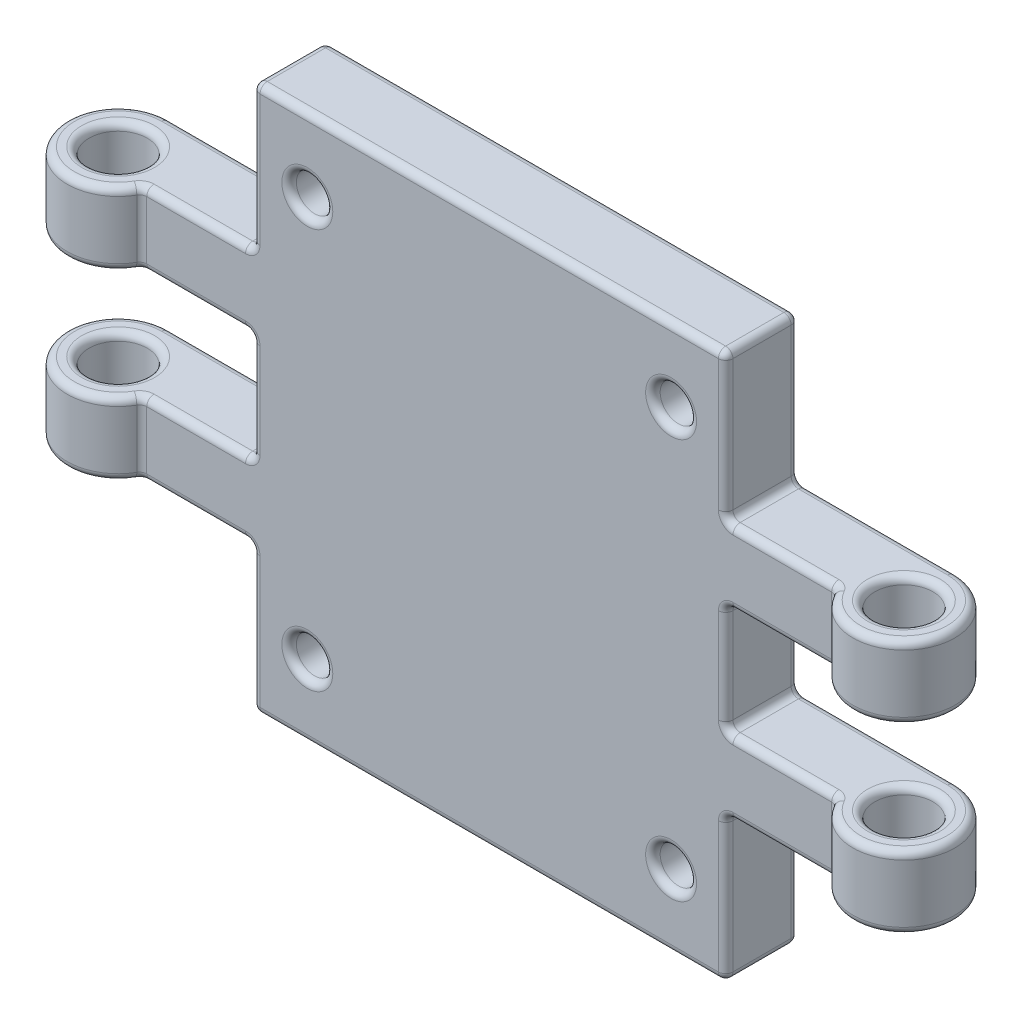
SolidWorks part; units mm, degrees
ref_plane "Front Plane" through (0, 0, 0) normal (0, 0, 1) x (1, 0, 0)
ref_plane "Top Plane" through (0, 0, 0) normal (0, 1, 0) x (1, 0, 0)
ref_plane "Right Plane" through (0, 0, 0) normal (1, 0, 0) x (0, 0, -1)
sketch "Sketch1" plane through (0, 0, 0) normal (0, 0, 1) x (1, 0, 0)
  line L0 (-47.5, 7.5) -> (-47.5, 17.5)
  line L1 (-47.5, -17.5) -> (47.5, -17.5)
  line L2 (-47.5, -17.5) -> (-47.5, 17.5) construction
  line L3 (-47.5, 17.5) -> (47.5, 17.5)
  line L4 (47.5, -17.5) -> (47.5, 17.5) construction
  line L5 (-47.5, -17.5) -> (47.5, 17.5) construction
  line L6 (-47.5, 17.5) -> (47.5, -17.5) construction
  line L7 (60.5, 7.5) -> (47.5, 7.5)
  line L8 (60.5, 7.5) -> (60.5, 17.5)
  line L9 (60.5, 17.5) -> (47.5, 17.5)
  line L10 (47.5, 7.5) -> (47.5, 17.5)
  line L11 (60.5, 7.5) -> (47.5, 17.5) construction
  line L12 (60.5, 17.5) -> (47.5, 7.5) construction
  line L13 (60.5, -7.5) -> (47.5, -7.5)
  line L14 (60.5, -7.5) -> (60.5, -17.5)
  line L15 (60.5, -17.5) -> (47.5, -17.5)
  line L16 (47.5, -7.5) -> (47.5, -17.5)
  line L17 (60.5, -7.5) -> (47.5, -17.5) construction
  line L18 (60.5, -17.5) -> (47.5, -7.5) construction
  line L19 (-60.5, 7.5) -> (-47.5, 7.5)
  line L20 (-60.5, 7.5) -> (-60.5, 17.5)
  line L21 (-60.5, 17.5) -> (-47.5, 17.5)
  line L22 (-47.5, 7.5) -> (-47.5, 17.5)
  line L23 (-60.5, 7.5) -> (-47.5, 17.5) construction
  line L24 (-60.5, 17.5) -> (-47.5, 7.5) construction
  line L25 (-60.5, -7.5) -> (-47.5, -7.5)
  line L26 (-60.5, -7.5) -> (-60.5, -17.5)
  line L27 (-60.5, -17.5) -> (-47.5, -17.5)
  line L28 (-47.5, -7.5) -> (-47.5, -17.5)
  line L29 (-60.5, -7.5) -> (-47.5, -17.5) construction
  line L30 (-60.5, -17.5) -> (-47.5, -7.5) construction
  line L33 (47.5, 17.5) -> (-47.5, 17.5)
  line L35 (-32.5, 37.5) -> (-32.5, 17.5)
  line L36 (-32.5, 37.5) -> (32.5, 37.5)
  line L39 (-47.5, -17.5) -> (47.5, -17.5)
  line L41 (32.5, 37.5) -> (32.5, 17.5)
  line L42 (55, 0) -> (-55, 0) construction
  line L43 (-47.5, -7.5) -> (-47.5, -17.5)
  line L44 (47.5, 17.5) -> (47.5, 7.5)
  line L45 (47.5, -7.5) -> (47.5, -17.5)
  line L46 (47.5, -7.5) -> (32.5, -7.5)
  line L47 (32.5, -7.5) -> (32.5, 7.5)
  line L48 (32.5, 7.5) -> (47.5, 7.5)
  line L49 (-47.5, 7.5) -> (-32.5, 7.5)
  line L50 (-32.5, 7.5) -> (-32.5, -7.5)
  line L51 (-32.5, -7.5) -> (-47.5, -7.5)
  line L52 (-54, -12.5) -> (54, -12.5) construction
  line L53 (-54, 12.5) -> (54, 12.5) construction
  line L54 (-32.5, -37.5) -> (-32.5, -17.5)
  line L55 (32.5, -37.5) -> (32.5, -17.5)
  line L56 (-32.5, -37.5) -> (32.5, -37.5)
  point P0 (0, 0)
  point P6 (54, 12.5)
  point P7 (54, -12.5)
  point P11 (-54, 12.5)
  point P15 (-54, -12.5)
  dimension "D1" = 20
  dimension "D2" = 108
  dimension "D3" = 10
  dimension "D4" = 15
  dimension "D6" = 13
  dimension "D7" = 15
extrude "Boss-Extrude1" add sketch "Sketch1" along normal blind 10 contours L10 L7 L8 L9 | L50 L51 L28 L1 L16 L46 L47 L48 L10 L3 L0 L49 | L13 L16 L15 L14 | L21 L20 L19 L0 | L28 L25 L26 L27 | L41 L36 L35 L33 | L54 L56 L55 L39 region at (-54, 12.5, 0) region at (0, 0, 0) region at (0, 27.5, 0) region at (-54, -12.5, 0) region at (54, 12.5, 0) region at (0, -27.5, 0) region at (54, -12.5, 0)
sketch "Sketch2" plane through (0, 0, 0) normal (0, -1, 0) x (1, 0, 0)
  line L0 (-60.5, 0) -> (-32.5, 0) construction
  circle A0 centre (-54, 7) radius 4
  circle A1 centre (-54, 7) radius 7
  circle A5 centre (54, 7) radius 4
  circle A6 centre (54, 7) radius 7
  dimension "D1" = 8
  dimension "D4" = 3
  dimension "D2" = 3
  dimension "D3" = 8
  dimension "D5" = 54
  dimension "D6" = 54
extrude "Boss-Extrude2" add sketch "Sketch2" against normal blind 17.5 and the other way blind 17.5
sketch "Sketch3" plane through (0, 0, 10) normal (0, 0, 1) x (1, 0, 0)
  line L0 (-61, 17.5) -> (-61, -17.5) construction
  line L1 (-61, -7.5) -> (-32.5, -7.5)
  line L2 (-61, -7.5) -> (-61, 7.5)
  line L3 (-61, 7.5) -> (-32.5, 7.5)
  line L4 (-32.5, -7.5) -> (-32.5, 7.5)
  line L5 (-61, -7.5) -> (-32.5, 7.5) construction
  line L6 (-61, 7.5) -> (-32.5, -7.5) construction
  line L7 (0, 0) -> (0, 17.5) construction
  line L8 (-25, 27.5) -> (-25, -27.5) construction
  line L9 (-32.5, 37.5) -> (-32.5, 17.5) construction
  line L11 (61, 7.5) -> (32.5, -7.5) construction
  line L12 (61, -7.5) -> (32.5, 7.5) construction
  line L13 (32.5, -7.5) -> (32.5, 7.5)
  line L14 (61, 7.5) -> (32.5, 7.5)
  line L15 (61, -7.5) -> (61, 7.5)
  line L16 (61, -7.5) -> (32.5, -7.5)
  line L17 (-25, 27.5) -> (25, 27.5) construction
  line L19 (25, 27.5) -> (25, -27.5) construction
  circle A0 centre (-25, -27.5) radius 2.5
  circle A1 centre (-25, 27.5) radius 2.5
  circle A2 centre (25, 27.5) radius 2.5
  circle A3 centre (25, -27.5) radius 2.5
  point P0 (-46.75, 0)
  point P10 (-25, 0)
  point P20 (46.75, 0)
  dimension "D2" = 5
  dimension "D1" = 15
  dimension "D3" = 55
  dimension "D4" = 50
  dimension "D5" = 25
extrude "Cut-Extrude2" cut sketch "Sketch3" against normal blind 35 and the other way blind 35
sketch "Sketch4" plane through (0, -17.5, 0) normal (0, -1, 0) x (1, 0, 0)
  circle A0 centre (-54, 7) radius 7
  circle A1 centre (-54, 7) radius 4
  line M3 (-60.3246, 10) -> (-60.5, 10)
  line M4 (-60.5, 10) -> (-60.5, 9.5981)
  line M6 (-60.5, 4.4019) -> (-60.5, 0)
  line M7 (-60.5, 0) -> (-32.5, 0)
  line M9 (-51.3542, 10) -> (-56.6458, 10)
  dimension "D1" = 3
  dimension "D2" = 8
extrude "Cut-Extrude3" cut sketch "Sketch4" against normal through all contours A0 M6 M7 | A1 M9 | A0 M3 M4 region at (-60.4423, -17.5, 9.868) region at (-58.9934, -17.5, 1.1973) region at (-54, -17.5, 6.7353)
sketch "Sketch5" plane through (0, -17.5, 0) normal (0, -1, 0) x (1, 0, 0)
  circle A0 centre (54, 7) radius 4
  circle A1 centre (54, 7) radius 7
  line M1 (56.6458, 10) -> (51.3542, 10)
  line M3 (60.5, 0) -> (60.5, 4.4019)
  line M5 (60.5, 9.5981) -> (60.5, 10)
  line M6 (60.5, 10) -> (60.3246, 10)
  line M10 (32.5, 0) -> (60.5, 0)
  dimension "D1" = 8
  dimension "D2" = 3
extrude "Cut-Extrude4" cut sketch "Sketch5" against normal through all contours A1 M10 M3 | A0 M1 | A1 M5 M6 region at (54, -17.5, 6.7353) region at (60.4423, -17.5, 9.868) region at (58.9934, -17.5, 1.1973)
fillet "Fillet1" radius 1 72 edges at (43.25, 17.5, 0) (32.5, 27.5, 0) (0, 37.5, 0) (-43.25, 17.5, 0) (-43.25, -7.5, 0) (32.5, -27.5, 0) (43.25, -7.5, 0) (32.5, 0, 0) (32.5, -7.5, 5) (32.5, 37.5, 5) (32.5, 17.5, 5) (59.9161, -7.5, 10.7417) (59.9161, 7.5, 10.7417) (-59.9161, -7.5, 10.7417) (-59.9161, 7.5, 10.7417) (-22.5, -27.5, 0) (-22.5, -27.5, 10) (-22.5, 27.5, 0) (-22.5, 27.5, 10) (27.5, 27.5, 0) (27.5, 27.5, 10) (27.5, -27.5, 0) (27.5, -27.5, 10) (59.9161, -17.5, 10.7417) (54, -17.5, 3) (59.9161, 17.5, 10.7417) (54, 17.5, 3) (47.6754, 12.5, 10) (47.6754, -12.5, 10) (-54, 17.5, 3) (-59.9161, 17.5, 10.7417) (-54, -17.5, 3) (-59.9161, -17.5, 10.7417) (-47.6754, -12.5, 10) (-47.6754, 12.5, 10) (-32.5, 27.5, 0) (-43.25, 7.5, 0) (-32.5, 0, 0) (-43.25, -17.5, 0) (-32.5, -27.5, 0) (0, -37.5, 0) (43.25, -17.5, 0) (43.25, 7.5, 0) (40.0877, 17.5, 10) (32.5, 27.5, 10) (0, 37.5, 10) (-32.5, 27.5, 10) (-40.0877, 17.5, 10) (-40.0877, 7.5, 10) (-32.5, 0, 10) (-40.0877, -7.5, 10) (-40.0877, -17.5, 10) (-32.5, -27.5, 10) (0, -37.5, 10) (32.5, -27.5, 10) (40.0877, -17.5, 10) (40.0877, -7.5, 10) (32.5, 0, 10) (40.0877, 7.5, 10) (32.5, 7.5, 5) (32.5, -17.5, 5) (32.5, -37.5, 5) (-32.5, -37.5, 5) (-32.5, -17.5, 5) (-32.5, -7.5, 5) (-32.5, 7.5, 5) (-32.5, 17.5, 5) (-32.5, 37.5, 5) (50, -7.5, 7) (58, 7.5, 7) (-54, -7.5, 11) (-54, 7.5, 3)
